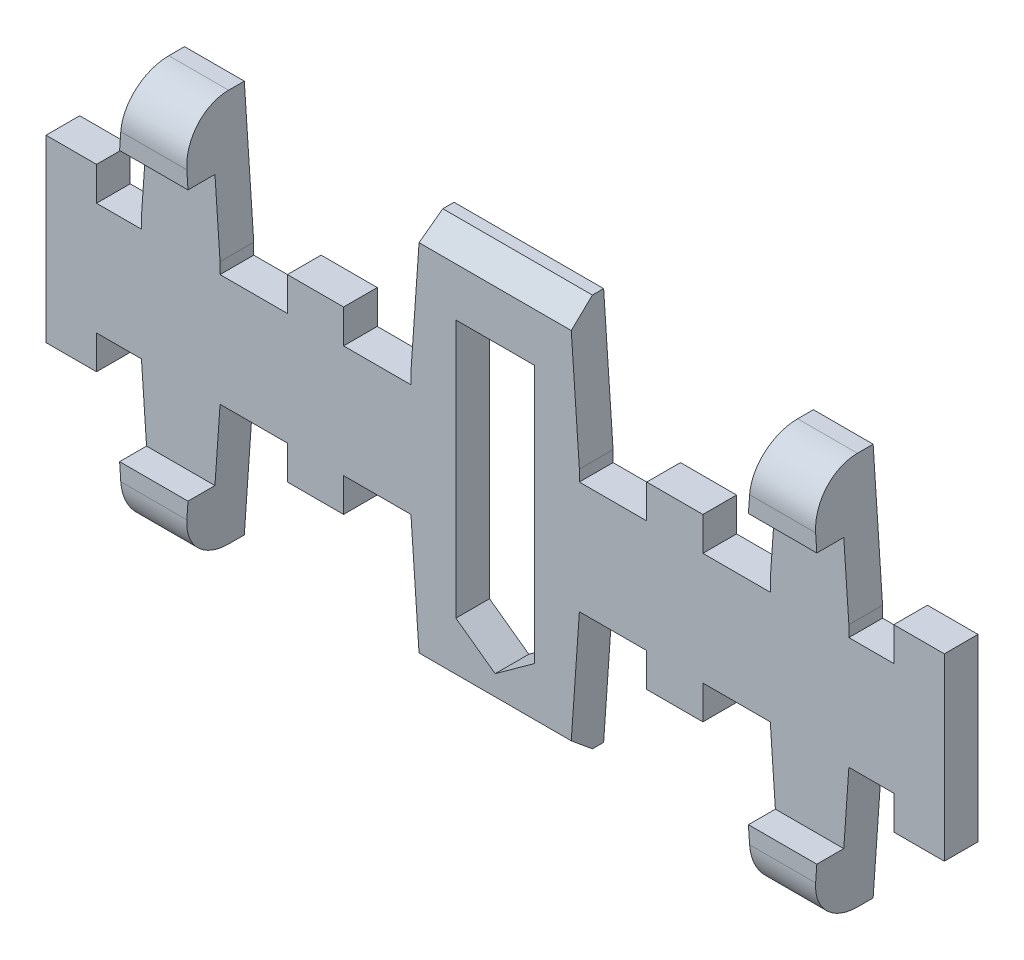
SolidWorks part; units mm, degrees
ref_plane "Plano frontal" through (0, 0, 0) normal (0, 0, 1) x (1, 0, 0)
ref_plane "Plano superior" through (0, 0, 0) normal (0, 1, 0) x (1, 0, 0)
ref_plane "Plano direito" through (0, 0, 0) normal (1, 0, 0) x (0, 0, -1)
sketch "Esboço10" plane through (0, 0, 0) normal (0, 0, 1) x (1, 0, 0)
  line L1 (-20, 8.75) -> (20, 8.75)
  line L2 (-20, 8.75) -> (-20, -8.75)
  line L3 (-20, -8.75) -> (20, -8.75)
  line L4 (20, 8.75) -> (20, -8.75)
  line L5 (-20, 8.75) -> (20, -8.75) construction
  line L6 (-20, -8.75) -> (20, 8.75) construction
  point P0 (0, 0)
  dimension "D1" = 40
  dimension "D2" = 17.5
extrude "Ressalto-extrusão6" add sketch "Esboço10" along normal blind 1.5
sketch "Esboço11" plane through (0, 0, 1.5) normal (0, 0, 1) x (1, 0, 0)
  line L0 (-20, 3.75) -> (-15.75, 3.75)
  line L1 (-20, 8.75) -> (-20, -8.75) construction
  line L2 (-15.75, 3.75) -> (-15.75, 8.75)
  line L3 (20, 8.75) -> (-20, 8.75) construction
  line L4 (-15.75, 8.75) -> (-12.25, 8.75)
  line L5 (-12.25, 8.75) -> (-12.25, 3.75)
  line L6 (-12.25, 3.75) -> (-3.75, 3.75)
  line L7 (-3.75, 3.75) -> (-3.75, 9.75)
  line L8 (-3.75, 9.75) -> (3.75, 9.75)
  line L9 (3.75, 9.75) -> (3.75, 3.75)
  line L10 (3.75, 3.75) -> (12.25, 3.75)
  line L11 (12.25, 3.75) -> (12.25, 8.75)
  line L12 (12.25, 8.75) -> (15.75, 8.75)
  line L13 (15.75, 8.75) -> (15.75, 3.75)
  line L14 (15.75, 3.75) -> (20, 3.75)
  line L15 (20, -8.75) -> (20, 8.75) construction
  line L16 (20, 3.75) -> (20, 11.9024)
  line L17 (20, 11.9024) -> (-20, 11.9024)
  line L18 (-20, 11.9024) -> (-20, 3.75)
  line L20 (-20, -4.25) -> (-15.75, -4.25)
  line L21 (-15.75, -4.25) -> (-15.75, -8.75)
  line L22 (-20, -8.75) -> (20, -8.75) construction
  line L23 (-15.75, -8.75) -> (-12.25, -8.75)
  line L24 (-12.25, -8.75) -> (-12.25, -4.25)
  line L25 (-12.25, -4.25) -> (-3.75, -4.25)
  line L26 (-3.75, -4.25) -> (-3.75, -10.25)
  line L27 (-3.75, -10.25) -> (3.75, -9.7467)
  line L28 (3.75, -9.7467) -> (3.75, -4.25)
  line L29 (3.75, -4.25) -> (12.25, -4.25)
  line L30 (12.25, -4.25) -> (12.25, -8.75)
  line L31 (12.25, -8.75) -> (15.75, -8.75)
  line L32 (15.75, -8.75) -> (15.75, -4.25)
  line L33 (15.75, -4.25) -> (20, -4.25)
  line L34 (20, -4.25) -> (20, -11.3192)
  line L35 (20, -11.3192) -> (-20, -11.3192)
  line L36 (-20, -11.3192) -> (-20, -4.25)
  dimension "D1" = 4.25
  dimension "D2" = 3.5
  dimension "D3" = 8.5
  dimension "D4" = 7.5
  dimension "D5" = 8.5
  dimension "D6" = 3.5
  dimension "D7" = 8
  dimension "D8" = 5
  dimension "D9" = 6
  dimension "D10" = 6
extrude "Corte-extrusão2" cut sketch "Esboço11" against normal blind 2.5
sketch "Esboço12" plane through (0, 0, 1.5) normal (0, 0, 1) x (1, 0, 0)
  line L0 (-12.25, 8.75) -> (-12.25, 3.75) construction
  line L1 (-15.75, 8.75) -> (-12.25, 8.75)
  line L2 (-15.75, 8.75) -> (-15.75, 6)
  line L3 (-15.75, 6) -> (-12.25, 6)
  line L4 (-12.25, 8.75) -> (-12.25, 6)
  line L6 (-15.75, -8.75) -> (-12.25, -8.75)
  line L7 (-15.75, -8.75) -> (-15.75, -6)
  line L8 (-15.75, -6) -> (-12.25, -6)
  line L9 (-12.25, -8.75) -> (-12.25, -6)
  line L11 (12.25, -8.75) -> (15.75, -8.75)
  line L12 (12.25, -8.75) -> (12.25, -6)
  line L13 (12.25, -6) -> (15.75, -6)
  line L14 (15.75, -8.75) -> (15.75, -6)
  line L16 (12.25, 8.75) -> (15.75, 8.75)
  line L17 (12.25, 8.75) -> (12.25, 6)
  line L18 (12.25, 6) -> (15.75, 6)
  line L19 (15.75, 8.75) -> (15.75, 6)
  dimension "D1" = 2.75
  dimension "D2" = 2.75
  dimension "D3" = 2.75
  dimension "D4" = 2.75
extrude "Ressalto-extrusão7" add sketch "Esboço12" along normal blind 1.2
sketch "Esboço13" plane through (0, 0, 1.5) normal (0, 0, 1) x (1, 0, 0)
  line L1 (-12.25, 3.75) -> (-9.25, 3.75)
  line L2 (-12.25, 3.75) -> (-12.25, 2.25)
  line L3 (-12.25, 2.25) -> (-9.25, 2.25)
  line L4 (-9.25, 3.75) -> (-9.25, 2.25)
  line L5 (-3.75, 3.75) -> (-6.75, 3.75)
  line L6 (-3.75, 3.75) -> (-3.75, 2.25)
  line L7 (-3.75, 2.25) -> (-6.75, 2.25)
  line L8 (-6.75, 3.75) -> (-6.75, 2.25)
  line L9 (3.75, 3.75) -> (6.75, 3.75)
  line L10 (3.75, 3.75) -> (3.75, 2.25)
  line L11 (3.75, 2.25) -> (6.75, 2.25)
  line L12 (6.75, 3.75) -> (6.75, 2.25)
  line L13 (12.25, 3.75) -> (9.25, 3.75)
  line L14 (12.25, 3.75) -> (12.25, 2.25)
  line L15 (12.25, 2.25) -> (9.25, 2.25)
  line L16 (9.25, 3.75) -> (9.25, 2.25)
  line L17 (12.25, -4.25) -> (9.25, -4.25)
  line L18 (12.25, -4.25) -> (12.25, -2.75)
  line L19 (12.25, -2.75) -> (9.25, -2.75)
  line L20 (9.25, -4.25) -> (9.25, -2.75)
  line L21 (3.75, -4.25) -> (6.75, -4.25)
  line L22 (3.75, -4.25) -> (3.75, -2.75)
  line L23 (3.75, -2.75) -> (6.75, -2.75)
  line L24 (6.75, -4.25) -> (6.75, -2.75)
  line L25 (-3.75, -4.25) -> (-6.75, -4.25)
  line L26 (-3.75, -4.25) -> (-3.75, -2.75)
  line L27 (-3.75, -2.75) -> (-6.75, -2.75)
  line L28 (-6.75, -4.25) -> (-6.75, -2.75)
  line L29 (-12.25, -4.25) -> (-9.25, -4.25)
  line L30 (-12.25, -4.25) -> (-12.25, -2.75)
  line L31 (-12.25, -2.75) -> (-9.25, -2.75)
  line L32 (-9.25, -4.25) -> (-9.25, -2.75)
  line L33 (-15.75, -4.25) -> (-17.75, -4.25)
  line L34 (-15.75, -4.25) -> (-15.75, -2.75)
  line L35 (-15.75, -2.75) -> (-17.75, -2.75)
  line L36 (-17.75, -4.25) -> (-17.75, -2.75)
  line L37 (-15.75, 3.75) -> (-17.75, 3.75)
  line L38 (-15.75, 3.75) -> (-15.75, 2.25)
  line L39 (-15.75, 2.25) -> (-17.75, 2.25)
  line L40 (-17.75, 3.75) -> (-17.75, 2.25)
  line L41 (15.75, 3.75) -> (17.75, 3.75)
  line L42 (15.75, 3.75) -> (15.75, 2.25)
  line L43 (15.75, 2.25) -> (17.75, 2.25)
  line L44 (17.75, 3.75) -> (17.75, 2.25)
  line L45 (15.75, -4.25) -> (17.75, -4.25)
  line L46 (15.75, -4.25) -> (15.75, -2.75)
  line L47 (15.75, -2.75) -> (17.75, -2.75)
  line L48 (17.75, -4.25) -> (17.75, -2.75)
  dimension "D1" = 2
  dimension "D2" = 3
  dimension "D3" = 3
  dimension "D4" = 3
  dimension "D5" = 3
  dimension "D6" = 2
  dimension "D7" = 1.5
  dimension "D8" = 1.5
extrude "Corte-extrusão3" cut sketch "Esboço13" against normal blind 8
sketch "Esboço15" plane through (0, 0, 1.5) normal (0, 0, 1) x (1, 0, 0)
  line L0 (3.75, 8.75) -> (-3.75, 8.75) construction
  line L1 (-1.75, 5.75) -> (1.75, 5.75)
  line L2 (-1.75, 5.75) -> (-1.75, -5.75)
  line L3 (-1.75, -5.75) -> (0, -7.015)
  line L4 (1.75, 5.75) -> (1.75, -5.75)
  line L6 (-3.75, -8.75) -> (-3.75, -2.75) construction
  line L7 (3.75, -2.75) -> (3.75, -8.75) construction
  line L8 (0, -7.015) -> (1.75, -5.75)
  dimension "D1" = 3
  dimension "D3" = 2
  dimension "D4" = 2
extrude "Corte-extrusão4" cut sketch "Esboço15" against normal blind 20
chamfer "Chanfro5" distance 6 angle 4 12 edges at (-15.75, -8.75, 1.35) (-3.75, -8.75, 0.75) (12.25, -8.75, 1.35) (15.75, 8.75, 1.35) (3.75, 8.75, 0.75) (-12.25, 8.75, 1.35) (-12.25, -8.75, 1.35) (3.75, -8.75, 0.75) (15.75, -8.75, 1.35) (12.25, 8.75, 1.35) (-3.75, 8.75, 0.75) (-15.75, 8.75, 1.35)
chamfer "Chanfro6" distance 1 angle 40 2 edges at (0, -8.75, 1.5) (0, 8.75, 1.5)
fillet "Filete1" radius 2 4 edges at (-14, -8.75, 2.7) (-14, 8.75, 2.7) (14, 8.75, 2.7) (14, -8.75, 2.7)
